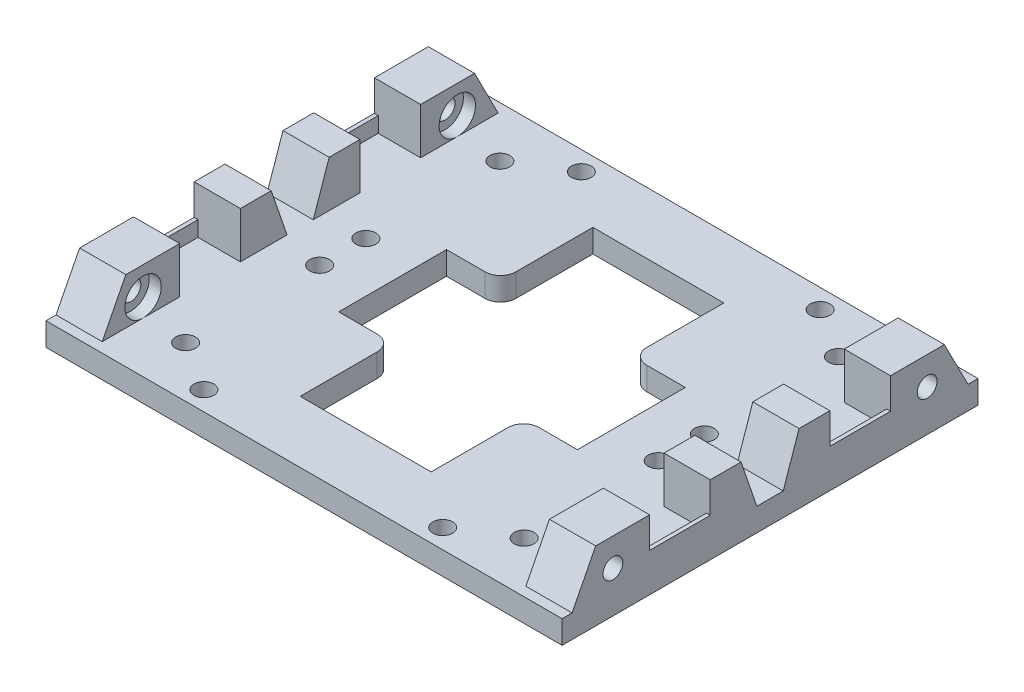
SolidWorks part; units mm, degrees
material "ABS"
ref_plane "Front Plane" through (0, 0, 0) normal (0, 0, 1) x (1, 0, 0)
ref_plane "Top Plane" through (0, 0, 0) normal (0, 1, 0) x (1, 0, 0)
ref_plane "Right Plane" through (0, 0, 0) normal (1, 0, 0) x (0, 0, -1)
sketch "Sketch1" plane through (0, 0, 0) normal (0, 1, 0) x (1, 0, 0)
  line L1 (0, 0) -> (85.09, 0)
  line L2 (0, 0) -> (0, 68.58)
  line L3 (0, 68.58) -> (85.09, 68.58)
  line L4 (85.09, 0) -> (85.09, 68.58)
  dimension "D1" = 68.58
  dimension "D2" = 85.09
extrude "Boss-Extrude1" add sketch "Sketch1" along normal blind 5.08
hole_wizard "#30 (0.1285) Diameter Hole1" positions "3DSketch1" profile "Sketch2" hole size "#30" standard "ANSI Inch" end condition through all
sketch3d "3DSketch1"
  line L0 (0, 5.08, -68.58) -> (0, 5.08, 0) construction
  line L1 (85.09, 5.08, 0) -> (85.09, 5.08, -68.58) construction
  line L2 (85.09, 5.08, -68.58) -> (0, 5.08, -68.58) construction
  line L3 (0, 5.08, 0) -> (85.09, 5.08, 0) construction
  point P0 (62.23, 5.08, -65.405)
  point P2 (22.86, 5.08, -65.405)
  point P4 (22.86, 5.08, -3.175)
  point P6 (62.23, 5.08, -3.175)
  dimension "D1" = 22.86
  dimension "D2" = 22.86
  dimension "D3" = 3.175
  dimension "D4" = 3.175
  dimension "D5" = 22.86
  dimension "D6" = 22.86
  dimension "D7" = 3.175
  dimension "D8" = 3.175
sketch "Sketch2" plane through (62.23, 5.08, -65.405) normal (1, 0, 0) x (0, 0, 1)
  line L0 (0, 0) -> (0, 5.08)
  line L1 (0, 5.08) -> (1.6319, 5.08)
  line L2 (1.6319, 5.08) -> (1.6319, 0)
  line L5 (1.6319, 0) -> (0, 0)
  line L11 (0, -6.35) -> (0, 107.95) construction
  dimension "Thru Hole Dia." = 3.2639
  dimension "Thru Hole Depth" = 5.08
sketch "Sketch3" plane through (0, 5.08, 0) normal (0, 1, 0) x (1, 0, 0)
  line L0 (85.09, 0) -> (85.09, 68.58) construction
  line L1 (85.09, 0) -> (53.213, 0)
  line L2 (85.09, 0) -> (85.09, 68.58)
  line L3 (85.09, 68.58) -> (53.213, 68.58)
  line L4 (0, 0) -> (0, 68.58)
  line L5 (0, 68.58) -> (0, 0) construction
  line L6 (0, 0) -> (85.09, 0) construction
  line L7 (85.09, 68.58) -> (0, 68.58) construction
  line L8 (53.213, 68.58) -> (0, 68.58)
  line L10 (53.213, 0) -> (53.213, 68.58)
  line L12 (53.213, 0) -> (53.213, 68.58)
  line L13 (53.213, 0) -> (0, 0)
  line M10 (0, 0) -> (85.09, 0)
  line M12 (85.09, 68.58) -> (0, 68.58)
  dimension "D1" = 0
  dimension "D2" = 0
  dimension "D3" = 0
  dimension "D4" = 0
  dimension "D5" = 31.877
  dimension "D6" = 0
extrude "Cut-Extrude1" cut sketch "Sketch3" against normal blind 1.27 contours L10 L2 M10 M12 | L10 L4 M10 M12 region at (69.1515, 5.08, -34.29) region at (26.6065, 5.08, -34.29)
hole_wizard "#30 (0.1285) Diameter Hole2" positions "3DSketch2" profile "Sketch4" hole size "#30" standard "ANSI Inch" end condition through all
sketch3d "3DSketch2"
  line L10 (85.09, 3.81, -68.58) -> (0, 3.81, -68.58) construction
  line L11 (0, 3.81, 0) -> (85.09, 3.81, 0) construction
  point P0 (70.455, 3.81, -38.1)
  point P10 (70.455, 3.81, -60.198)
  point P12 (70.455, 3.81, -30.48)
  point P14 (70.455, 3.81, -8.382)
  point P16 (14.635, 3.81, -8.382)
  point P18 (14.635, 3.81, -30.48)
  point P20 (14.635, 3.81, -38.1)
  point P22 (14.635, 3.81, -60.198)
  dimension "D3" = 8.382
  dimension "D2" = 22.098
  dimension "D14" = 22.098
  dimension "D17" = 14.635
  dimension "D4" = 14.635
  dimension "D5" = 14.635
  dimension "D6" = 14.635
  dimension "D7" = 14.635
  dimension "D8" = 14.635
  dimension "D9" = 14.635
  dimension "D10" = 8.382
  dimension "D11" = 14.635
  dimension "D12" = 8.382
  dimension "D13" = 8.382
  dimension "D15" = 22.098
  dimension "D16" = 22.098
sketch "Sketch4" plane through (70.455, 3.81, -38.1) normal (1, 0, 0) x (0, 0, 1)
  line L0 (0, 0) -> (0, 3.81)
  line L1 (0, 3.81) -> (1.6319, 3.81)
  line L2 (1.6319, 3.81) -> (1.6319, 0)
  line L5 (1.6319, 0) -> (0, 0)
  line L11 (0, -6.35) -> (0, 107.95) construction
  dimension "Thru Hole Dia." = 3.2639
  dimension "Thru Hole Depth" = 3.81
sketch "Sketch9" plane through (0, 0, 0) normal (-1, 0, 0) x (0, 0, 1)
  line L0 (-14.431, 3.81) -> (-1.651, 3.81)
  line L3 (-14.431, 11.43) -> (-14.431, 3.81)
  line L4 (-68.58, 0) -> (0, 0) construction
  line L5 (-14.431, 11.43) -> (-5.541, 11.43)
  line L6 (-5.541, 11.43) -> (-1.651, 3.81)
  line L7 (-19.431, 22.5435) -> (-19.431, -8.657) construction
  line L8 (0, 3.81) -> (0, 0) construction
  line L9 (-68.58, 3.81) -> (0, 3.81) construction
  line L10 (-24.431, 3.81) -> (-24.431, 11.43)
  line L11 (-24.431, 11.43) -> (-29.511, 11.43)
  line L12 (-29.511, 11.43) -> (-32.131, 3.81)
  line L13 (-32.131, 3.81) -> (-24.431, 3.81)
  line L14 (-49.149, 20.6807) -> (-49.149, -9.7425) construction
  line L15 (-68.58, 3.81) -> (-68.58, 0) construction
  line L16 (-44.149, 3.81) -> (-44.149, 11.43)
  line L17 (-44.149, 11.43) -> (-39.069, 11.43)
  line L18 (-39.069, 11.43) -> (-36.449, 3.81)
  line L19 (-36.449, 3.81) -> (-44.149, 3.81)
  line L20 (-54.149, 3.81) -> (-54.149, 11.43)
  line L21 (-54.149, 11.43) -> (-63.039, 11.43)
  line L22 (-63.039, 11.43) -> (-66.929, 3.81)
  line L23 (-66.929, 3.81) -> (-54.149, 3.81)
  dimension "D1" = 3.81
  dimension "D2" = 7.62
  dimension "D3" = 8.89
  dimension "D4" = 19.431
  dimension "D5" = 5
  dimension "D6" = 17.78
  dimension "D7" = 5
  dimension "D8" = 5.08
  dimension "D9" = 12.7
  dimension "D10" = 7.62
  dimension "D11" = 19.431
  dimension "D12" = 5
  dimension "D13" = 5
  dimension "D14" = 5.08
  dimension "D15" = 12.7
  dimension "D16" = 8.89
  dimension "D17" = 17.78
  dimension "D18" = 7.62
  dimension "D19" = 7.62
extrude "Boss-Extrude2" add sketch "Sketch9" against normal blind 7.62
sketch "Sketch10" plane through (0, 0, 0) normal (-1, 0, 0) x (0, 0, 1)
  line L0 (-44.149, 11.43) -> (-44.149, 3.81) construction
  line L1 (-54.149, 3.81) -> (-44.149, 3.81)
  line L2 (-54.149, 3.81) -> (-54.149, 6.35)
  line L3 (-54.149, 6.35) -> (-44.149, 6.35)
  line L4 (-44.149, 3.81) -> (-44.149, 6.35)
  line L5 (-14.431, 11.43) -> (-14.431, 3.81) construction
  line L6 (-24.431, 3.81) -> (-14.431, 3.81)
  line L7 (-24.431, 3.81) -> (-24.431, 6.35)
  line L8 (-24.431, 6.35) -> (-14.431, 6.35)
  line L9 (-14.431, 3.81) -> (-14.431, 6.35)
  dimension "D1" = 2.54
  dimension "D2" = 2.54
extrude "Boss-Extrude3" add sketch "Sketch10" against normal blind 0.635
sketch "Sketch11" plane through (85.09, 0, 0) normal (1, 0, 0) x (0, 0, -1)
  line L0 (1.651, 3.81) -> (5.541, 11.43) construction
  line L1 (14.431, 3.81) -> (1.651, 3.81) construction
  line L6 (0, 3.81) -> (68.58, 3.81) construction
  line L10 (24.431, 3.81) -> (24.431, 11.43)
  line L11 (24.431, 11.43) -> (29.511, 11.43)
  line L12 (29.511, 11.43) -> (32.1119, 3.81)
  line L13 (32.1119, 3.81) -> (24.431, 3.81)
  line L14 (44.149, 3.81) -> (44.149, 11.43)
  line L15 (54.149, 3.81) -> (44.149, 3.81) construction
  line L16 (44.149, 11.43) -> (39.069, 11.43)
  line L17 (39.069, 11.43) -> (36.4681, 3.81)
  line L18 (36.4681, 3.81) -> (44.149, 3.81)
  line L24 (14.431, 11.43) -> (14.431, 3.81)
  line L25 (24.431, 3.81) -> (14.431, 3.81) construction
  line L26 (14.431, 3.81) -> (1.651, 3.81)
  line L27 (1.651, 3.81) -> (5.541, 11.43)
  line L28 (5.541, 11.43) -> (14.431, 11.43)
  line L29 (63.039, 11.43) -> (66.929, 3.81)
  line L30 (66.929, 3.81) -> (54.149, 3.81)
  line L31 (54.149, 3.81) -> (54.149, 11.43)
  line L32 (54.149, 11.43) -> (63.039, 11.43)
  line L33 (66.929, 3.81) -> (54.149, 3.81) construction
extrude "Boss-Extrude4" add sketch "Sketch11" against normal blind 7.62
sketch "Sketch12" plane through (85.09, 0, 0) normal (1, 0, 0) x (0, 0, -1)
  line L1 (14.431, 3.81) -> (24.431, 3.81)
  line L2 (14.431, 3.81) -> (14.431, 6.35)
  line L3 (14.431, 6.35) -> (24.431, 6.35)
  line L4 (24.431, 3.81) -> (24.431, 6.35)
  line L5 (44.149, 3.81) -> (54.149, 3.81)
  line L6 (44.149, 3.81) -> (44.149, 6.35)
  line L7 (44.149, 6.35) -> (54.149, 6.35)
  line L8 (54.149, 3.81) -> (54.149, 6.35)
extrude "Boss-Extrude5" add sketch "Sketch12" against normal blind 0.635
sketch "Sketch13" plane through (0, 3.81, 0) normal (0, 1, 0) x (1, 0, 0)
  line L0 (0, 0) -> (85.09, 0) construction
  line L1 (31.75, 58.42) -> (53.34, 58.42)
  line L2 (31.75, 58.42) -> (31.75, 10.16)
  line L3 (31.75, 10.16) -> (53.34, 10.16)
  line L4 (53.34, 58.42) -> (53.34, 10.16)
  line L5 (22.86, 43.18) -> (62.23, 43.18)
  line L6 (22.86, 43.18) -> (22.86, 25.4)
  line L7 (22.86, 25.4) -> (62.23, 25.4)
  line L8 (62.23, 43.18) -> (62.23, 25.4)
  line L9 (85.09, 68.58) -> (0, 68.58) construction
  line L11 (85.09, 54.149) -> (85.09, 44.149) construction
  line L12 (0, 44.149) -> (0, 54.149) construction
  line L14 (85.09, 32.1119) -> (85.09, 36.4681) construction
  line L15 (0, 36.449) -> (0, 32.131) construction
  dimension "D1" = 10.16
  dimension "D2" = 10.16
  dimension "D3" = 31.75
  dimension "D4" = 31.75
  dimension "D5" = 25.4
  dimension "D6" = 25.4
  dimension "D7" = 22.86
  dimension "D8" = 22.86
extrude "Cut-Extrude3" cut sketch "Sketch13" against normal through all contours L2 L5 L4 L1 | L6 L7 L2 L5 | L2 L7 L4 L5 | L8 L5 L4 L7 | L7 L2 L3 L4 region at (42.545, 3.81, -50.8) region at (42.545, 3.81, -34.29) region at (27.305, 3.81, -34.29) region at (57.785, 3.81, -34.29) region at (42.545, 3.81, -17.78)
fillet "Fillet1" radius 2.54 4 edges at (31.75, 1.905, -43.18) (53.34, 1.905, -43.18) (53.34, 1.905, -25.4) (31.75, 1.905, -25.4)
sketch "Sketch14" plane through (85.09, 0, 0) normal (1, 0, 0) x (0, 0, -1)
  line L0 (0, 3.81) -> (1.651, 3.81) construction
  line L1 (0, 3.81) -> (0, 0) construction
  line L2 (68.58, 3.81) -> (68.58, 0) construction
  line L3 (66.929, 3.81) -> (68.58, 3.81) construction
  circle A0 centre (8.382, 6.81) radius 1.632
  circle A1 centre (8.382, 6.81) radius 3
  circle A2 centre (60.198, 6.81) radius 1.6319
  circle A3 centre (60.198, 6.81) radius 3
  dimension "D1" = 3.2639
  dimension "D2" = 6
  dimension "D4" = 6
  dimension "D5" = 3.2639
  dimension "D3" = 8.382
  dimension "D6" = 8.382
extrude "Cut-Extrude4" cut sketch "Sketch14" along normal through all both and the other way through all from surface contours A0 | A2 region at (85.09, 6.81, -8.382) region at (85.09, 6.81, -60.198) starting at face at (77.47, 7.62, -9.0135)
extrude "Cut-Extrude5" cut sketch "Sketch14<3>" along normal blind 2 from surface contours A1 A0 | A3 A2 region at (85.09, 6.81, -5.4669) region at (85.09, 6.81, -57.2829) starting at face at (77.47, 6.81, -6.75)
sketch "Sketch14<3>" plane through (85.09, 0, 0) normal (1, 0, 0) x (0, 0, -1) same geometry as "Sketch14"
extrude "Cut-Extrude6" cut sketch "Sketch14<4>" against normal blind 2 from surface contours A1 A0 | A3 A2 region at (85.09, 6.81, -5.4669) region at (85.09, 6.81, -57.2829) starting at face at (7.62, 6.81, -6.75)
sketch "Sketch14<4>" plane through (85.09, 0, 0) normal (1, 0, 0) x (0, 0, -1) same geometry as "Sketch14"
